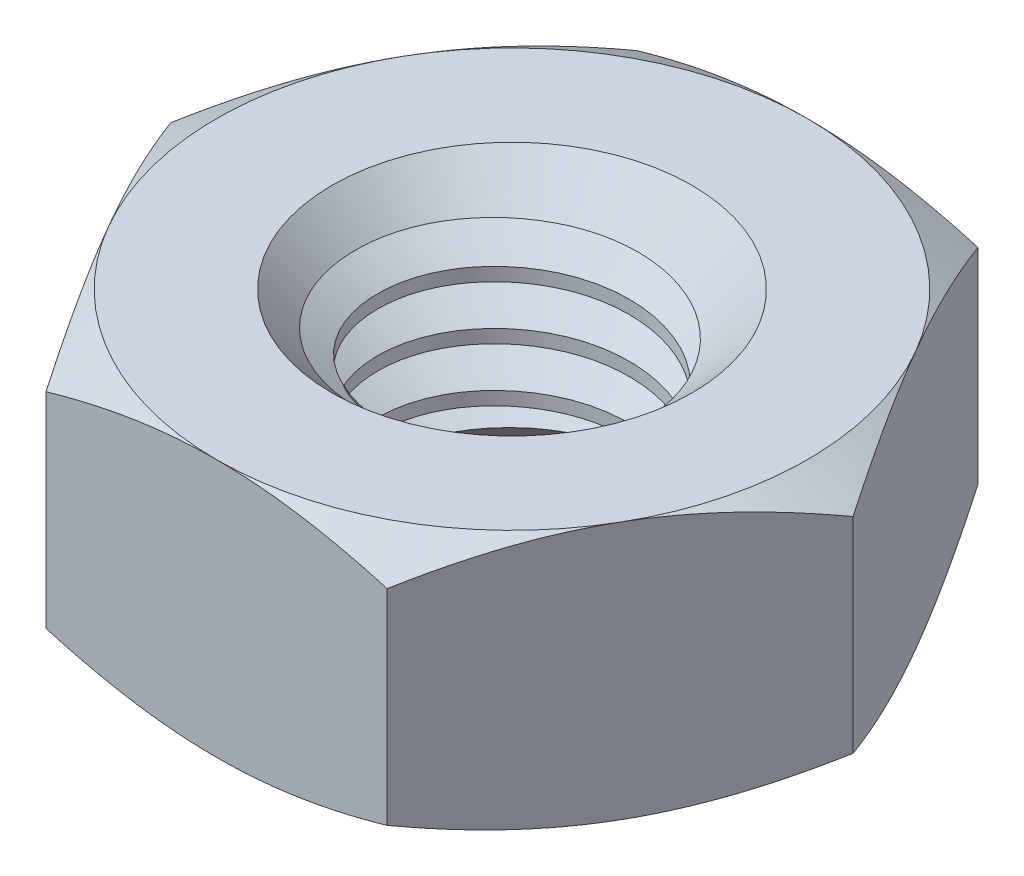
SolidWorks part; units mm, degrees
ref_plane "Front" through (0, 0, 0) normal (0, 0, 1) x (1, 0, 0)
ref_plane "Top" through (0, 0, 0) normal (0, 1, 0) x (1, 0, 0)
ref_plane "Right" through (0, 0, 0) normal (1, 0, 0) x (0, 0, -1)
sketch "Çizim1" plane through (0, 0, 0) normal (0, 0, 1) x (1, 0, 0)
  line L1 (3.1754, 0) -> (1.5877, 2.75)
  line L2 (1.5877, 2.75) -> (-1.5877, 2.75)
  line L3 (-1.5877, 2.75) -> (-3.1754, 0)
  line L4 (-3.1754, 0) -> (-1.5877, -2.75)
  line L5 (-1.5877, -2.75) -> (1.5877, -2.75)
  line L6 (1.5877, -2.75) -> (3.1754, 0)
  circle A0 centre (0, 0) radius 2.75 construction
  dimension "D1" = 5.5
extrude "Yükseklik-Ekstrüzyon1" add sketch "Çizim1" along normal blind 2.4
sketch "Çizim2" plane through (0, 0, 2.4) normal (0, 0, 1) x (1, 0, 0)
  circle A0 centre (0, 0) radius 2.75
extrude "Kes-Ekstrüzyon1" cut sketch "Çizim2" against normal blind 2.4 draft 60 flip side to cut
sketch "Çizim3" plane through (0, 0, 0) normal (0, 0, -1) x (-1, 0, 0)
  circle A0 centre (0, 0) radius 2.75
extrude "Kes-Ekstrüzyon2" cut sketch "Çizim3" against normal blind 2.4 draft 60 flip side to cut
sketch "Çizim4" plane through (0, 0, 0) normal (0, 0, -1) x (-1, 0, 0)
  circle A0 centre (0, 0) radius 1.175
  dimension "D1" = 2.35
extrude "Kes-Ekstrüzyon3" cut sketch "Çizim4" against normal blind 2.4
chamfer "Pah1" distance 0.5 angle 45 2 edges at (-1.175, 0, 2.4) (-1.175, 0, 0)
sketch "Çizim5" plane through (0, 0, 2.4) normal (0, 0, 1) x (1, 0, 0)
  circle A0 centre (0, 0) radius 1.175
curve "Helis/Spiral1" pitch 0.5 height 3 radius 1.175 centre (0, 0, 2.4) axis (0, 0, -1) start towards (-1, 0, 0)
ref_plane "Düzlem1" through (-1.175, 0, -0.6) normal (0, 0.9977, -0.0676) x (1, 0, 0)
sketch "Çizim6" plane through (-1.175, 0, -0.6) normal (0, 0.9977, -0.0676) x (1, 0, 0)
  line L1 (-0.325, 0) -> (0.0987, -0.2446)
  line L3 (0.0987, 0.2446) -> (-0.325, 0)
  line L4 (0.0987, 0.2446) -> (0.0987, -0.2446)
  line L5 (0.1625, 0) -> (0.1625, 0.2815) [skipped]
  circle A0 centre (0, 0) radius 0.1625 construction
  dimension "D1" = 0.325
sweep "Kes-Süpür1" cut profiles "Çizim6" path "Helis/Spiral1" align with end faces yes
move or copy body "Body-Move/Copy1" bodies to move or copy 105 copy no rotation origin (0, 0, 1.1993) rotation axis (1, 0, 0) rotation angle 90
